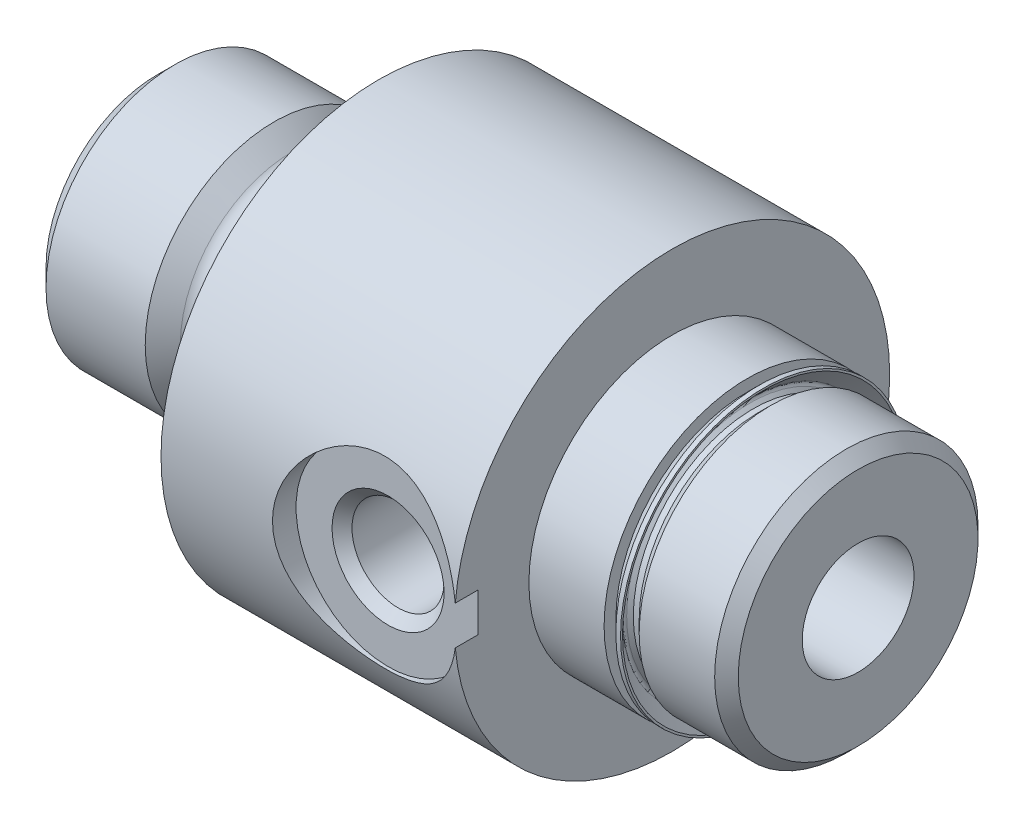
SolidWorks part; units mm, degrees
material "AISI 304"
ref_plane "Front Plane" through (0, 0, 0) normal (0, 0, 1) x (1, 0, 0)
ref_plane "Top Plane" through (0, 0, 0) normal (0, 1, 0) x (1, 0, 0)
ref_plane "Right Plane" through (0, 0, 0) normal (1, 0, 0) x (0, 0, -1)
sketch "Sketch1" plane through (0, 0, 0) normal (0, 0, 1) x (1, 0, 0)
  line L0 (0, 0) -> (0, 4.8006)
  line L1 (0, 4.8006) -> (0.7557, 5.5563)
  line L2 (0.7557, 5.5563) -> (5.0286, 5.5563)
  line L3 (5.0286, 5.5563) -> (5.7864, 4.8042)
  line L4 (6.35, 4.572) -> (7.5184, 4.572)
  line L5 (8.3185, 5.3721) -> (8.3185, 5.5245)
  line L6 (8.3185, 5.5245) -> (9.525, 5.5245)
  line L7 (9.525, 5.5245) -> (9.525, 0)
  line L8 (9.525, 0) -> (0, 0)
  line L9 (9.525, 0) -> (0, 0) construction
  arc A0 (5.7864, 4.8042) -> (6.35, 4.572) centre (6.35, 5.3721) ccw
  arc A1 (7.5184, 4.572) -> (8.3185, 5.3721) centre (7.5184, 5.3721) ccw
revolve "Revolve1" add sketch "Sketch1" angle 360 about L9 reverse direction yes
cosmetic thread "Cosmetic Thread1"
sketch "Sketch2" plane through (0, 0, 0) normal (0, 0, 1) x (1, 0, 0)
  line L0 (9.525, 0) -> (9.525, 9.3726)
  line L1 (9.525, 9.3726) -> (25.4, 9.3726)
  line L2 (25.4, 9.3726) -> (25.4, 5.1626)
  line L3 (25.4, 5.1626) -> (25.908, 5.1626)
  line L4 (25.908, 5.1626) -> (26.416, 5.6706)
  line L5 (26.416, 5.6706) -> (29.6672, 5.6706)
  line L6 (29.6672, 5.6706) -> (30.1752, 5.1626)
  line L7 (30.1752, 5.1626) -> (30.1752, 0)
  line L8 (30.1752, 0) -> (9.525, 0)
  line L9 (30.1752, 0) -> (9.525, 0) construction
revolve "Revolve2" add sketch "Sketch2" angle 360 about L9 reverse direction yes
hole_wizard "Hole1" positions "Sketch4" profile "Sketch3" legacy
sketch "Sketch4" plane through (0, 0, 0) normal (-1, 0, 0) x (0, 0, 1)
  point P0 (0, 0)
sketch "Sketch3" plane through (0, 0, 0) normal (0, 1, 0) x (0, 0, 1)
  line L0 (0, 0) -> (0, 30.1752)
  line L1 (0, 30.1752) -> (2.4066, 30.1752)
  line L2 (2.4066, 30.1752) -> (2.4067, 0.508)
  line L3 (2.4067, 0.508) -> (2.9147, 0)
  line L4 (2.9147, 0) -> (0, 0)
  line L5 (0, -6.4453) -> (0, 115.525) construction
  line L6 (-2.4067, 0.508) -> (-2.9147, 0) construction
  dimension "Diameter" = 4.8133
  dimension "Depth" = 30.1752
  dimension "C-Sink Angle" = 90
  dimension "C-Sink Diameter" = 5.8293
sketch "Sketch5" plane through (0, 0, 0) normal (0, 1, 0) x (1, 0, 0)
  line L0 (18.288, 1.016) -> (20.2717, 1.016)
  line L1 (20.2717, 1.016) -> (20.2717, -7.9273)
  line L2 (20.2717, -7.9273) -> (20.701, -8.3566)
  line L3 (20.701, -8.3566) -> (22.2504, -8.3566)
  line L4 (22.2504, -8.3566) -> (22.2504, -9.3726)
  line L5 (22.2504, -9.3726) -> (18.288, -9.3726)
  line L6 (18.288, -9.3726) -> (18.288, 1.016)
  line L7 (18.288, -9.3726) -> (18.288, 1.016) construction
revolve "Cut-Revolve1" cut sketch "Sketch5" angle 360 about L7 reverse direction yes
cosmetic thread "Cosmetic Thread2" parameters "D1"=4.7752, "D2"=4.826
sketch "Sketch6" plane through (0, 0, 0) normal (0, 0, 1) x (1, 0, 0)
  line L0 (22.1615, 6.1658) -> (25.4, 6.1658)
  line L1 (25.4, 6.1658) -> (25.4, 9.9758)
  line L2 (25.4, 9.9758) -> (22.1615, 9.9758)
  line L3 (22.1615, 9.9758) -> (22.1615, 6.1658)
  line L4 (25.4, 0) -> (22.1615, 0) construction
revolve "Cut-Revolve2" cut sketch "Sketch6" angle 360 about L4 reverse direction yes
ref_plane "Plane1" through (7.9248, 0, 0) normal (1, 0, 0) x (0, 0, -1)
ref_plane "Plane2" through (19.05, 0, 0) normal (1, 0, 0) x (0, 0, -1)
ref_plane "Plane3" through (0, 0, 0) normal (0, -0.7071, 0.7071) x (1, 0, 0)
ref_plane "Plane4" through (1.5748, 0, 0) normal (1, 0, 0) x (0, 0, -1)
ref_plane "Plane5" through (25.4, 0, 0) normal (1, 0, 0) x (0, 0, -1)
ref_plane "Plane6" through (9.525, 0, 0) normal (1, 0, 0) x (0, 0, -1)
ref_plane "Plane7" through (25.4, 0, 0) normal (1, 0, 0) x (0, 0, -1)
sketch "Sketch7" plane through (0, 0, 0) normal (0, 0, 1) x (1, 0, 0)
  line L0 (25.4, 4.9085) -> (25.908, 4.9085)
  line L1 (25.908, 4.9085) -> (25.908, 5.1626)
  line L2 (25.908, 5.1626) -> (25.654, 5.1626)
  line L3 (25.654, 5.1626) -> (25.5116, 5.305)
  line L4 (25.5116, 5.4846) -> (26.1087, 6.0817)
  line L5 (26.1087, 6.0817) -> (26.1087, 6.1658)
  line L6 (26.1087, 6.1658) -> (25.9055, 6.1658)
  line L7 (25.9055, 6.1658) -> (25.4, 5.6603)
  line L8 (25.4, 5.6603) -> (25.4, 4.9085)
  line L9 (25.908, 0) -> (25.4, 0) construction
  arc A0 (25.5116, 5.305) -> (25.5116, 5.4846) centre (25.6014, 5.3948) cw
revolve "Revolve3" add sketch "Sketch7" angle 360 about L9 reverse direction yes
ref_plane "Plane8" through (25.908, 0, 0) normal (1, 0, 0) x (0, 0, -1)
ref_plane "Plane9" through (9.525, 0, 0) normal (1, 0, 0) x (0, 0, -1)
ref_plane "Plane10" through (8.3185, 0, 0) normal (1, 0, 0) x (0, 0, -1)
ref_plane "Plane11" through (0, 9.525, 0) normal (0, 1, 0) x (1, 0, 0)
ref_plane "Plane12" through (0, -9.525, 0) normal (0, 1, 0) x (1, 0, 0)
ref_plane "Plane13" through (9.525, 0, 0) normal (1, 0, 0) x (0, 0, -1)
ref_plane "Plane14" through (0, 0, 0) normal (0, 0, 1) x (1, 0, 0)
ref_plane "Plane15" through (0, 0, 0) normal (0, 1, 0) x (1, 0, 0)
ref_plane "Plane16" through (0, 0, 0) normal (0, 1, 0) x (1, 0, 0)
ref_plane "Plane17" through (0, 0, 0) normal (0, 1, 0) x (1, 0, 0)
ref_plane "Plane18" through (0, 0, 0) normal (1, 0, 0) x (0, 0, -1)
ref_plane "dp1 XY" through (0, 0, 0) normal (0, 0, 1) x (1, 0, 0)
ref_plane "dp1 XZ" through (0, 5.5245, 0) normal (0, -1, 0) x (-1, 0, 0)
ref_plane "dp1 YZ" through (9.525, 0, 0) normal (1, 0, 0) x (0, 0, -1)
ref_axis "dp1 X" through (-80.9, 5.5245, 0) along (1, 0, 0)
ref_axis "dp1 Y" through (9.525, -50, 0) along (0, 1, 0)
ref_axis "dp1 Z" through (9.525, 5.5245, 80.9) along (0, 0, -1)
sketch3d "dp1"
  point P0 (9.525, 5.5245, 0)
ref_plane "dp2 XY" through (0, 0, 0) normal (0, 0, 1) x (1, 0, 0)
ref_plane "dp2 XZ" through (0, -5.5245, 0) normal (0, -1, 0) x (-1, 0, 0)
ref_plane "dp2 YZ" through (9.525, 0, 0) normal (1, 0, 0) x (0, 0, -1)
ref_axis "dp2 X" through (-80.9, -5.5245, 0) along (1, 0, 0)
ref_axis "dp2 Y" through (9.525, -50, 0) along (0, 1, 0)
ref_axis "dp2 Z" through (9.525, -5.5245, 80.9) along (0, 0, -1)
sketch3d "dp2"
  point P0 (9.525, -5.5245, 0)
ref_plane "port XY" through (0, 0, 0) normal (0, 0, 1) x (1, 0, 0)
ref_plane "port XZ" through (0, 0, 0) normal (0, -1, 0) x (-1, 0, 0)
ref_plane "port YZ" through (18.288, 0, 0) normal (1, 0, 0) x (0, 0, -1)
ref_axis "port X" through (-80.9, 0, 0) along (1, 0, 0)
ref_axis "port Y" through (18.288, -50, 0) along (0, 1, 0)
ref_axis "port Z" through (18.288, 0, 80.9) along (0, 0, -1)
sketch3d "port"
  point P0 (18.288, 0, 0)
ref_plane "rod_guide XY" through (0, 0, 0) normal (1, 0, 0) x (0, 0, -1)
ref_plane "rod_guide XZ" through (0, 0, 0) normal (0, -1, 0) x (-1, 0, 0)
ref_plane "rod_guide YZ" through (0, 0, 0) normal (0, 0, -1) x (-1, 0, 0)
ref_axis "rod_guide X" through (0, 0, 80.9) along (0, 0, -1)
ref_axis "rod_guide Y" through (0, -50, 0) along (0, 1, 0)
ref_axis "rod_guide Z" through (80.9, 0, 0) along (-1, 0, 0)
sketch3d "rod_guide"
  point P0 (0, 0, 0)
ref_plane "s1 XY" through (0, 0, 0) normal (0, 0, 1) x (1, 0, 0)
ref_plane "s1 XZ" through (0, 0, 0) normal (0, -1, 0) x (-1, 0, 0)
ref_plane "s1 YZ" through (8.3185, 0, 0) normal (1, 0, 0) x (0, 0, -1)
ref_axis "s1 X" through (-80.9, 0, 0) along (1, 0, 0)
ref_axis "s1 Y" through (8.3185, -50, 0) along (0, 1, 0)
ref_axis "s1 Z" through (8.3185, 0, 80.9) along (0, 0, -1)
sketch3d "s1"
  point P0 (8.3185, 0, 0)
ref_plane "s2 XY" through (0, 0, 0) normal (0, 0, 1) x (1, 0, 0)
ref_plane "s2 XZ" through (0, 0, 0) normal (0, -1, 0) x (-1, 0, 0)
ref_plane "s2 YZ" through (9.525, 0, 0) normal (1, 0, 0) x (0, 0, -1)
ref_axis "s2 X" through (-80.9, 0, 0) along (1, 0, 0)
ref_axis "s2 Y" through (9.525, -50, 0) along (0, 1, 0)
ref_axis "s2 Z" through (9.525, 0, 80.9) along (0, 0, -1)
sketch3d "s2"
  point P0 (9.525, 0, 0)
ref_plane "t1 XY" through (9.525, 0, 0) normal (1, 0, 0) x (0, 0, -1)
ref_plane "t1 XZ" through (0, 0, 0) normal (0, -1, 0) x (-1, 0, 0)
ref_plane "t1 YZ" through (0, 0, 0) normal (0, 0, -1) x (-1, 0, 0)
ref_axis "t1 X" through (9.525, 0, 80.9) along (0, 0, -1)
ref_axis "t1 Y" through (9.525, -50, 0) along (0, 1, 0)
ref_axis "t1 Z" through (80.9, 0, 0) along (-1, 0, 0)
sketch3d "t1"
  point P0 (9.525, 0, 0)
ref_plane "t111 XY" through (9.525, 0, 0) normal (1, 0, 0) x (0, 0, -1)
ref_plane "t111 XZ" through (0, 0, 0) normal (0, -1, 0) x (-1, 0, 0)
ref_plane "t111 YZ" through (0, 0, 0) normal (0, 0, -1) x (-1, 0, 0)
ref_axis "t111 X" through (9.525, 0, 80.9) along (0, 0, -1)
ref_axis "t111 Y" through (9.525, -50, 0) along (0, 1, 0)
ref_axis "t111 Z" through (80.9, 0, 0) along (-1, 0, 0)
sketch3d "t111"
  point P0 (9.525, 0, 0)
ref_plane "to_foot_bracket XY" through (9.525, 0, 0) normal (1, 0, 0) x (0, 0, -1)
ref_plane "to_foot_bracket XZ" through (0, 0, 0) normal (0, -1, 0) x (-1, 0, 0)
ref_plane "to_foot_bracket YZ" through (0, 0, 0) normal (0, 0, -1) x (-1, 0, 0)
ref_axis "to_foot_bracket X" through (9.525, 0, 80.9) along (0, 0, -1)
ref_axis "to_foot_bracket Y" through (9.525, -50, 0) along (0, 1, 0)
ref_axis "to_foot_bracket Z" through (80.9, 0, 0) along (-1, 0, 0)
sketch3d "to_foot_bracket"
  point P0 (9.525, 0, 0)
ref_plane "to_nut XY" through (8.3185, 0, 0) normal (1, 0, 0) x (0, 0, -1)
ref_plane "to_nut XZ" through (0, 0, 0) normal (0, -1, 0) x (-1, 0, 0)
ref_plane "to_nut YZ" through (0, 0, 0) normal (0, 0, -1) x (-1, 0, 0)
ref_axis "to_nut X" through (8.3185, 0, 80.9) along (0, 0, -1)
ref_axis "to_nut Y" through (8.3185, -50, 0) along (0, 1, 0)
ref_axis "to_nut Z" through (80.9, 0, 0) along (-1, 0, 0)
sketch3d "to_nut"
  point P0 (8.3185, 0, 0)
ref_plane "to_rod XY" through (0, 0, 0) normal (1, 0, 0) x (0, 0, -1)
ref_plane "to_rod XZ" through (0, 0, 0) normal (0, -1, 0) x (-1, 0, 0)
ref_plane "to_rod YZ" through (0, 0, 0) normal (0, 0, -1) x (-1, 0, 0)
ref_axis "to_rod X" through (0, 0, 80.9) along (0, 0, -1)
ref_axis "to_rod Y" through (0, -50, 0) along (0, 1, 0)
ref_axis "to_rod Z" through (80.9, 0, 0) along (-1, 0, 0)
sketch3d "to_rod"
  point P0 (0, 0, 0)
ref_plane "to_screw XY" through (0, 0, 0) normal (0, 1, 0) x (1, 0, 0)
ref_plane "to_screw XZ" through (0, 0, 0) normal (0, 0, 1) x (1, 0, 0)
ref_plane "to_screw YZ" through (18.288, 0, 0) normal (1, 0, 0) x (0, 0, -1)
ref_axis "to_screw X" through (-80.9, 0, 0) along (1, 0, 0)
ref_axis "to_screw Y" through (18.288, 0, 50) along (0, 0, -1)
ref_axis "to_screw Z" through (18.288, 50, 0) along (0, -1, 0)
sketch3d "to_screw"
  point P0 (18.288, 0, 0)
ref_plane "to_trunnion_brackets XY" through (0, 0, 0) normal (0, 1, 0) x (1, 0, 0)
ref_plane "to_trunnion_brackets XZ" through (0, 0, 0) normal (0, 0, 1) x (1, 0, 0)
ref_plane "to_trunnion_brackets YZ" through (7.9248, 0, 0) normal (1, 0, 0) x (0, 0, -1)
ref_axis "to_trunnion_brackets X" through (-80.9, 0, 0) along (1, 0, 0)
ref_axis "to_trunnion_brackets Y" through (7.9248, 0, 50) along (0, 0, -1)
ref_axis "to_trunnion_brackets Z" through (7.9248, 50, 0) along (0, -1, 0)
sketch3d "to_trunnion_brackets"
  point P0 (7.9248, 0, 0)
ref_plane "to_trunnion_brackets1 XY" through (0, 9.525, 0) normal (0, 1, 0) x (1, 0, 0)
ref_plane "to_trunnion_brackets1 XZ" through (0, 0, 0) normal (0, 0, 1) x (1, 0, 0)
ref_plane "to_trunnion_brackets1 YZ" through (7.9248, 0, 0) normal (1, 0, 0) x (0, 0, -1)
ref_axis "to_trunnion_brackets1 X" through (-80.9, 9.525, 0) along (1, 0, 0)
ref_axis "to_trunnion_brackets1 Y" through (7.9248, 9.525, 50) along (0, 0, -1)
ref_axis "to_trunnion_brackets1 Z" through (7.9248, 50, 0) along (0, -1, 0)
sketch3d "to_trunnion_brackets1"
  point P0 (7.9248, 9.525, 0)
ref_plane "to_trunnion_brackets2 XY" through (0, -9.525, 0) normal (0, 1, 0) x (1, 0, 0)
ref_plane "to_trunnion_brackets2 XZ" through (0, 0, 0) normal (0, 0, 1) x (1, 0, 0)
ref_plane "to_trunnion_brackets2 YZ" through (7.9248, 0, 0) normal (1, 0, 0) x (0, 0, -1)
ref_axis "to_trunnion_brackets2 X" through (-80.9, -9.525, 0) along (1, 0, 0)
ref_axis "to_trunnion_brackets2 Y" through (7.9248, -9.525, 50) along (0, 0, -1)
ref_axis "to_trunnion_brackets2 Z" through (7.9248, 50, 0) along (0, -1, 0)
sketch3d "to_trunnion_brackets2"
  point P0 (7.9248, -9.525, 0)
ref_plane "to_tube XY" through (25.908, 0, 0) normal (1, 0, 0) x (0, 0, -1)
ref_plane "to_tube XZ" through (0, 0, 0) normal (0, -1, 0) x (-1, 0, 0)
ref_plane "to_tube YZ" through (0, 0, 0) normal (0, 0, -1) x (-1, 0, 0)
ref_axis "to_tube X" through (25.908, 0, 80.9) along (0, 0, -1)
ref_axis "to_tube Y" through (25.908, -50, 0) along (0, 1, 0)
ref_axis "to_tube Z" through (80.9, 0, 0) along (-1, 0, 0)
sketch3d "to_tube"
  point P0 (25.908, 0, 0)
